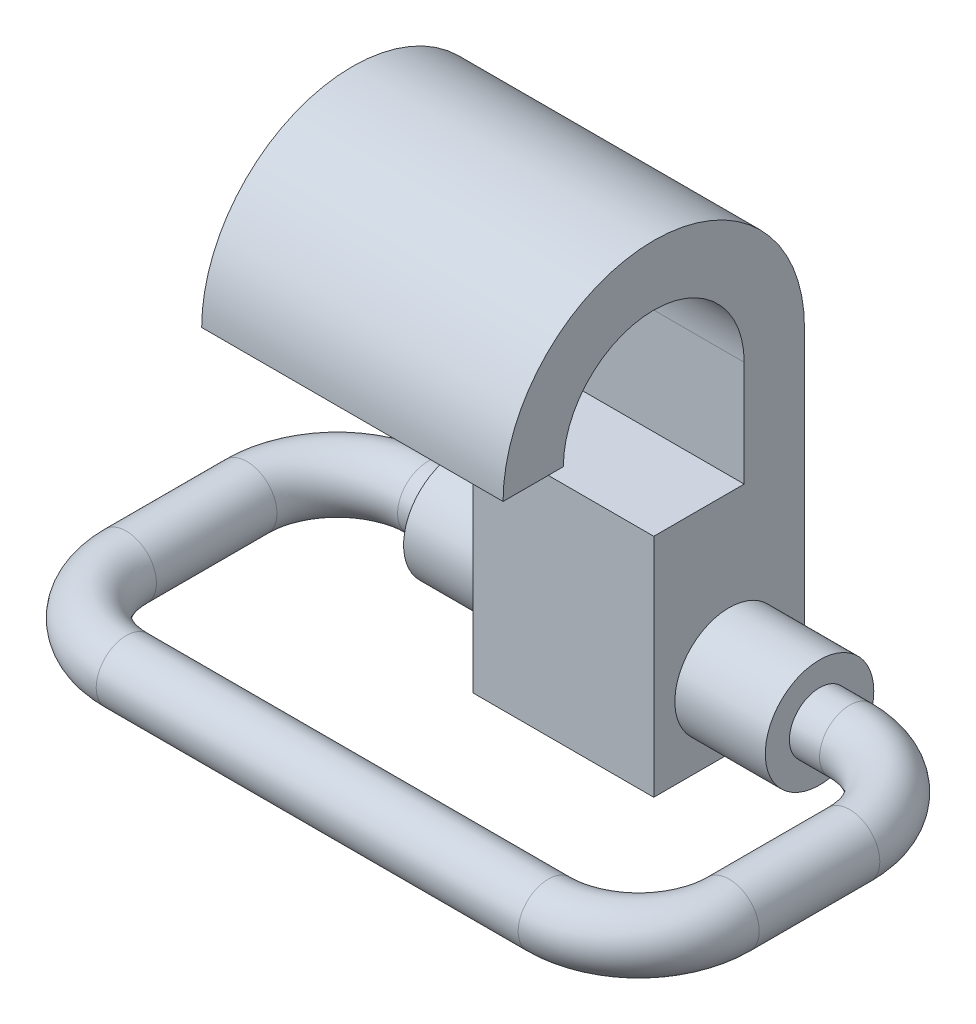
SolidWorks part; units mm, degrees
ref_plane "Plano frontal" through (0, 0, 0) normal (0, 0, 1) x (1, 0, 0)
ref_plane "Plano superior" through (0, 0, 0) normal (0, 1, 0) x (1, 0, 0)
ref_plane "Plano direito" through (0, 0, 0) normal (1, 0, 0) x (0, 0, -1)
sketch "Esboço1" plane through (0, 0, 0) normal (1, 0, 0) x (0, 0, -1)
  line L0 (-250, -375) -> (250, -375)
  line L1 (-250, -375) -> (-250, 375)
  line L2 (250, -375) -> (250, 375)
  line L3 (-250, 375) -> (250, 375)
  line L4 (-250, -375) -> (250, 375) construction
  line L5 (250, -375) -> (-250, 375) construction
  line L6 (250, -375) -> (0, -375) construction
  line L7 (0, -375) -> (0, -135) construction
  line L8 (250, 375) -> (50, 375) construction
  line L9 (50, 375) -> (250, 375)
  line L10 (50, 375) -> (50, 725)
  line L11 (250, 375) -> (250, 725)
  line L12 (50, 725) -> (250, 725)
  circle A0 centre (0, -135) radius 180
  circle A1 centre (0, -135) radius 100
  point P1 (0, 0)
  dimension "D4" = 360
  dimension "D5" = 200
  dimension "D1" = 750
  dimension "D2" = 500
  dimension "D3" = 240
  dimension "D6" = 200
  dimension "D7" = 350
extrude "Ressalto-extrusão2" add sketch "Esboço1" along normal blind 700 contours A1 region at (0, -135, 0)
extrude "Ressalto-extrusão6" add sketch "Esboço1<9>" along normal blind 600 contours A0 A1 region at (0, -135, 174.9088)
sketch "Esboço1<9>" plane through (0, 0, 0) normal (1, 0, 0) x (0, 0, -1) same geometry as "Esboço1"
extrude "Ressalto-extrusão7" add sketch "Esboço1<10>" along normal blind 300 contours L3 L1 L0 L2 A0 region at (0, 50.2954, 0)
sketch "Esboço1<10>" plane through (0, 0, 0) normal (1, 0, 0) x (0, 0, -1) same geometry as "Esboço1"
sketch "Esboço3" plane through (0, 375, 0) normal (0, 1, 0) x (1, 0, 0)
  line L0 (0, 250) -> (0, 50) construction
  line L1 (0, -250) -> (0, 250) construction
  line L3 (0, 50) -> (300, 50)
  line L4 (0, 50) -> (0, 250)
  line L5 (0, 250) -> (300, 250)
  line L6 (300, 50) -> (300, 250)
  dimension "D1" = 200
extrude "Ressalto-extrusão8" add sketch "Esboço3" along normal blind 350
sketch "Esboço5" plane through (300, 0, 0) normal (1, 0, 0) x (0, 0, -1)
  line L0 (50, 725) -> (-250, 725) construction
  line L1 (-750, 725) -> (-550, 725)
  line L2 (250, 725) -> (50, 725)
  arc A0 (50, 725) -> (-550, 725) centre (-250, 725) ccw
  arc A1 (250, 725) -> (-750, 725) centre (-250, 725) ccw
  dimension "D1" = 300
sketch "Esboço6" plane through (0, 0, 0) normal (-1, 0, 0) x (0, 0, 1)
  line L0 (-50, 725) -> (250, 725) construction
  line L1 (-250, 725) -> (-50, 725) construction
  line L2 (-50, 725) -> (-50, 375) construction
  dimension "D1" = 300
extrude "Ressalto-extrusão9" add sketch "Esboço5" against normal blind 300 contours A1 L1 A0 L2
sketch3d "3DSketch1" plane through (0, 0, 0) normal (0, 0, 1) x (1, 0, 0)
  dimension "D1" = 240
sketch "Esboço7" plane through (700, 0, 0) normal (1, 0, 0) x (0, 0, -1)
  point P0 (0, -135)
sketch "Esboço8" plane through (0, -135, 0) normal (0, -1, 0) x (-1, 0, 0)
  line L0 (-700, 0) -> (-700, -300) construction
  arc A0 (-700, 0) -> (-1000, -300) centre (-700, -300) ccw
  dimension "D1" = 300
sketch "Esboço9" plane through (700, 0, 0) normal (1, 0, 0) x (0, 0, -1)
  circle A0 centre (0, -135) radius 100
sweep "Varredura1" add profiles "Esboço9" path "Esboço8"
sketch "Esboço10" plane through (0, 0, 300) normal (0, 0, 1) x (1, 0, 0)
  circle A0 centre (1000, -135) radius 100
extrude "Ressalto-extrusão10" add sketch "Esboço10" along normal blind 400 contours A0
sketch "Esboço13" plane through (0, 0, 700) normal (0, 0, 1) x (1, 0, 0)
  point P0 (1000, -135)
sketch "Esboço14" plane through (0, -135, 0) normal (0, -1, 0) x (-1, 0, 0)
  line L0 (-1000, -700) -> (-700, -700) construction
  line L1 (-1100, -700) -> (-900, -700) construction
  arc A0 (-1000, -700) -> (-700, -1000) centre (-700, -700) ccw
  dimension "D1" = 300
sketch "Esboço15" plane through (0, 0, 700) normal (0, 0, 1) x (1, 0, 0)
  circle A0 centre (1000, -135) radius 100
sweep "Varredura2" add profiles "Esboço15" path "Esboço14"
sketch "Esboço17" plane through (700, 0, 0) normal (-1, 0, 0) x (0, 0, 1)
  circle A0 centre (1000, -135) radius 100
sketch "Esboço19" plane through (700, 0, 0) normal (-1, 0, 0) x (0, 0, 1)
extrude "Ressalto-extrusão11" add sketch "Esboço17" along normal blind 700
mirror "Espelhar1" of "Ressalto-extrusão11"
mirror "Espelhar2" of "Varredura2"
mirror "Espelhar3" of "Ressalto-extrusão10"
mirror "Espelhar4" of "Varredura1"
mirror "Espelhar5" of "Ressalto-extrusão2"
mirror "Espelhar6" of "Ressalto-extrusão6"
mirror "Espelhar7" of "Ressalto-extrusão9"
mirror "Espelhar8" about plane through (300, 0, 0) normal (1, 0, 0) of "Ressalto-extrusão2"
ref_plane "Plano1" through (0, -375, 250) normal (0, 1, 0) x (1, 0, 0)
sketch "Esboço21" plane through (0, 0, 0) normal (-1, 0, 0) x (0, 0, 1)
  line L0 (250, -375) -> (-250, -375) construction
  line L1 (250, 375) -> (-250, 375)
  line L2 (250, 375) -> (250, -375)
  line L3 (250, -375) -> (-250, -375)
  line L4 (-250, 375) -> (-250, -375)
  line L5 (-250, -375) -> (-250, 725) construction
extrude "Ressalto-extrusão12" add sketch "Esboço21" along normal blind 300
sketch "Esboço22" plane through (0, 0, 0) normal (-1, 0, 0) x (0, 0, 1)
  line L1 (-250, 725) -> (-50, 725)
  line L2 (-250, 725) -> (-250, 375)
  line L3 (-250, 375) -> (-50, 375)
  line L4 (-50, 725) -> (-50, 375)
extrude "Ressalto-extrusão13" add sketch "Esboço22" along normal blind 300
sketch "Esboço26" plane through (-300, 0, 0) normal (-1, 0, 0) x (0, 0, 1)
  line L0 (-250, 725) -> (-50, 725)
  line L1 (550, 725) -> (750, 725)
  arc A0 (750, 725) -> (-250, 725) centre (250, 725) ccw
  arc A1 (750, 725) -> (-250, 725) centre (250, 725) ccw construction
  arc A2 (550, 725) -> (-50, 725) centre (250, 725) ccw
  arc A3 (550, 725) -> (-50, 725) centre (250, 725) ccw construction
extrude "Ressalto-extrusão14" add sketch "Esboço26" along normal blind 400
sketch "Esboço30" plane through (-700, 0, 0) normal (-1, 0, 0) x (0, 0, 1)
  line L0 (-250, 725) -> (-50, 725) construction
  line L1 (-226.314, 1000) -> (-122.3909, 940)
  line L2 (-300, 725) -> (-180, 725)
  arc A0 (-180, 725) -> (-122.3909, 940) centre (250, 725) cw
  arc A1 (-300, 725) -> (-226.314, 1000) centre (250, 725) cw
  point P0 (250, 725)
